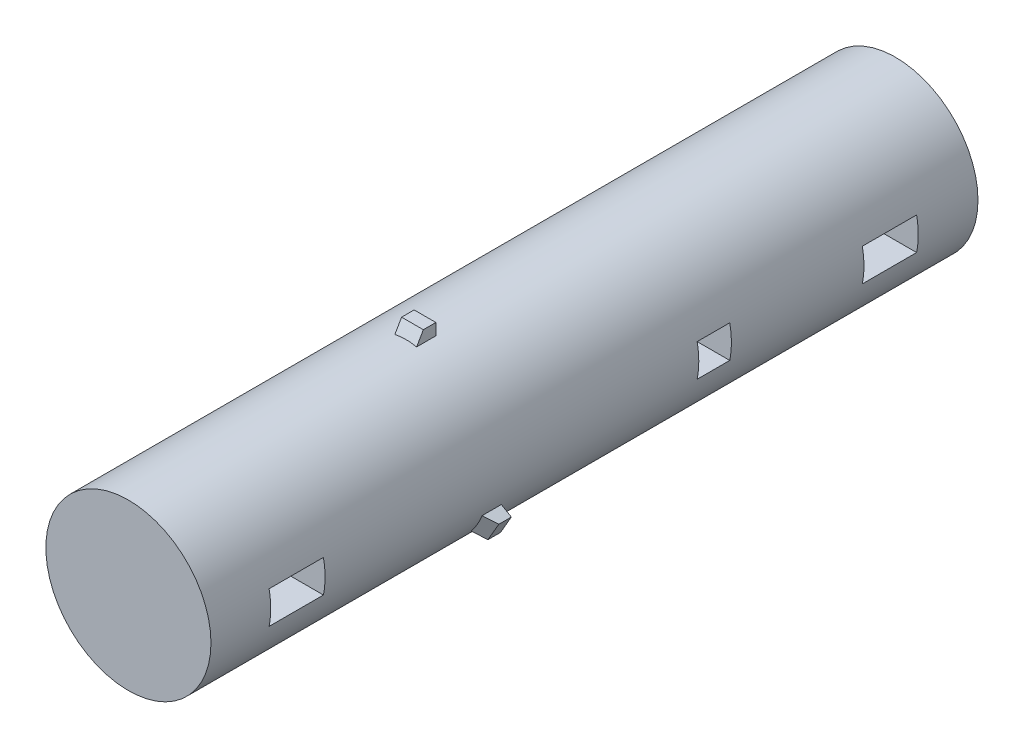
SolidWorks part; units mm, degrees
ref_plane "Front Plane" through (0, 0, 0) normal (0, 0, 1) x (1, 0, 0)
ref_plane "Top Plane" through (0, 0, 0) normal (0, 1, 0) x (1, 0, 0)
ref_plane "Right Plane" through (0, 0, 0) normal (1, 0, 0) x (0, 0, -1)
sketch "Sketch1" plane through (0, 0, 0) normal (0, 0, 1) x (1, 0, 0)
  circle A0 centre (0, 0) radius 3.8
  dimension "D1" = 7.6
extrude "Boss-Extrude1" add sketch "Sketch1" along normal blind 35.3
sketch "Sketch2" plane through (0, 0, 35.3) normal (0, 0, 1) x (1, 0, 0)
  line L0 (3.8, -3.8) -> (-3.8, -3.8)
  line L1 (3.8, -3.8) -> (3.8, 3.8)
  line L2 (-3.8, -3.8) -> (-3.8, 3.8)
  line L3 (3.8, 3.8) -> (-3.8, 3.8)
  line L4 (3.8, -3.8) -> (-3.8, 3.8) construction
  line L5 (-3.8, -3.8) -> (3.8, 3.8) construction
  circle A0 centre (0, 0) radius 3.8 construction
  point P1 (0, 0)
sketch "Sketch3" plane through (0, 0, 0) normal (1, 0, 0) x (0, 0, -1)
  line L0 (-35.3, 0) -> (0, 0)
  line L1 (-32.55, -0.75) -> (-30.05, -0.75)
  line L2 (-32.55, -0.75) -> (-32.55, 0.75)
  line L3 (-32.55, 0.75) -> (-30.05, 0.75)
  line L4 (-30.05, -0.75) -> (-30.05, 0.75)
  line L5 (-32.55, -0.75) -> (-30.05, 0.75) construction
  line L6 (-32.55, 0.75) -> (-30.05, -0.75) construction
  point P0 (-31.3, 0)
  dimension "D1" = 2.5
  dimension "D2" = 1.5
  dimension "D3" = 4
extrude "Cut-Extrude2" cut sketch "Sketch3" against normal through all both and the other way through all contours L1 L4 L0 L2 | L0 L4 L3 L2 region at (0, 0.375, 31.3) region at (0, -0.375, 31.3)
sketch "Sketch5" plane through (0, 0, 0) normal (0, 1, 0) x (1, 0, 0)
  line L0 (0, 0) -> (0, -35.3)
  point P4 (0, -17.65)
ref_plane "Plane2" through (0, 0, 17.65) normal (0, 0, 1) x (1, 0, 0)
mirror "Mirror1" about plane through (0, 0, 17.65) normal (0, 0, 1) of "Cut-Extrude2"
sketch "Sketch6" plane through (0, 0, 0) normal (1, 0, 0) x (0, 0, -1)
  line L0 (0, 3.8) -> (-35.3, 3.8) construction
  line L1 (-22.65, 3.8) -> (-12.65, 3.8)
  line L2 (-22.65, 3.8) -> (-22.65, -3.8)
  line L3 (-22.65, -3.8) -> (-12.65, -3.8)
  line L4 (-12.65, 3.8) -> (-12.65, -3.8)
  line L5 (-35.3, -3.8) -> (0, -3.8) construction
  line L6 (-35.3, 0) -> (0, 0) construction
  line L7 (-17.65, 0) -> (-17.65, 3.8)
  line L8 (-17.65, 4.18) -> (-17.65, -4.18) construction
  line L9 (0, 0) -> (-35.3, 0) construction
  line L10 (-12.85, -0.75) -> (-11.35, -0.75)
  line L11 (-12.85, -0.75) -> (-12.85, 0.75)
  line L12 (-12.85, 0.75) -> (-11.35, 0.75)
  line L13 (-11.35, -0.75) -> (-11.35, 0.75)
  line L14 (-12.85, -0.75) -> (-11.35, 0.75) construction
  line L15 (-12.85, 0.75) -> (-11.35, -0.75) construction
  point P17 (-12.1, 0)
  point P22 (0, 0)
  point P23 (-11.4232, 0)
  point P24 (-12.1142, 0)
  dimension "D1" = 10
  dimension "D2" = 1.5
  dimension "D3" = 1.5
  dimension "D4" = 0.2
extrude "Cut-Extrude3" cut sketch "Sketch6" against normal through all both and the other way through all contours L13 L12 L11 L10
sketch "Sketch7" plane through (0, 0, 0) normal (1, 0, 0) x (0, 0, -1)
  line L1 (-22.65, -3.8) -> (-12.65, -3.8) construction
  line L2 (-22.65, -3.8) -> (-22.65, 3.8) construction
  line L3 (-22.65, 3.8) -> (-12.65, 3.8) construction
  line L4 (-12.65, -3.8) -> (-12.65, 3.8) construction
  line L5 (-22.65, -3.8) -> (-12.65, 3.8) construction
  line L6 (-22.65, 3.8) -> (-12.65, -3.8) construction
  line L10 (-22.8047, 3.3) -> (-22.2274, 4.3)
  line L11 (-22.8047, 3.3) -> (-21.65, 3.3)
  line L12 (-22.8047, 3.3) -> (-22.8047, 4.3)
  line L13 (-22.8047, 4.3) -> (-21.65, 4.3)
  line L14 (-21.65, 3.3) -> (-21.65, 4.3)
  line L15 (0, 3.8) -> (-35.3, 3.8) construction
  line L16 (-12.85, -0.75) -> (-12.85, 0.75) construction
  point P0 (-17.65, 0)
  dimension "D1" = 10
  dimension "D2" = 8.8
  dimension "D3" = 0.5
  dimension "D4" = 60
  dimension "D5" = 0.5
extrude "Boss-Extrude2" add sketch "Sketch7" along normal mid plane 1 contours L3 L14 L13 L10 L11 L2 | L2 L1 L4 L3 region at (0, 3.7444, 22.0991)
pattern_circular "CirPattern1" count 3 over 360 about axis through (0, 0, 0) along (0, 0, 1) of "Boss-Extrude2" reverse direction yes
